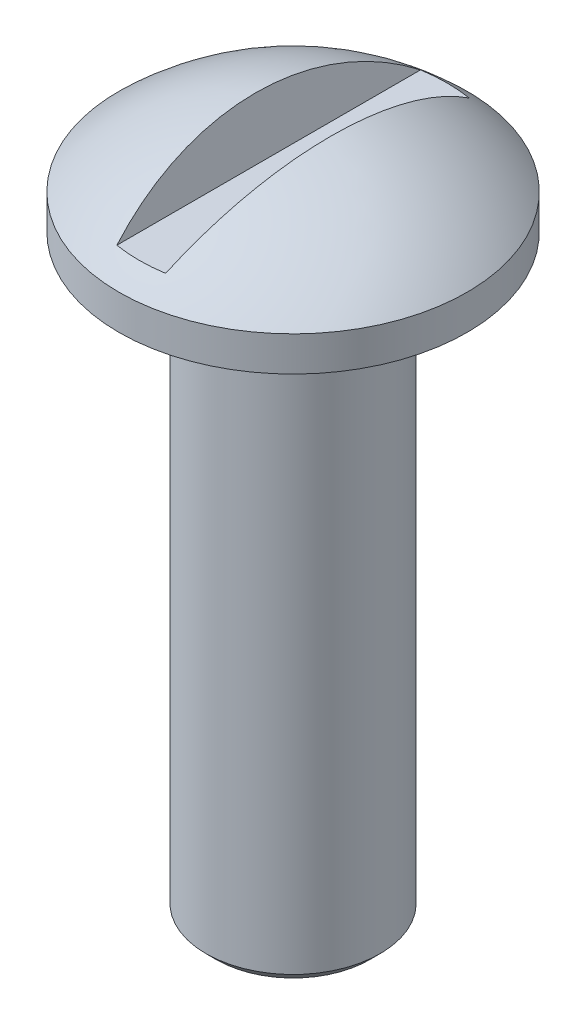
SolidWorks part; units mm, degrees
ref_plane "Front Plane" through (0, 0, 0) normal (0, 0, 1) x (1, 0, 0)
ref_plane "Top Plane" through (0, 0, 0) normal (0, 1, 0) x (1, 0, 0)
ref_plane "Right Plane" through (0, 0, 0) normal (1, 0, 0) x (0, 0, -1)
sketch "Sketch5" plane through (0, 0, 0) normal (0, 0, 1) x (1, 0, 0)
  line L0 (0, 0) -> (-6.35, 0)
  line L1 (-6.35, 0) -> (-6.35, 43.18)
  line L3 (0, 43.18) -> (0, 0)
  line L4 (0, 0) -> (0, -4.4813) construction
  line L5 (-6.35, 43.18) -> (-12.7, 43.18)
  line L6 (-12.7, 43.18) -> (-12.7, 45.72)
  line L7 (-12.7, 45.72) -> (0, 45.72)
  line L8 (0, 45.72) -> (0, 43.18)
  point P11 (-6.35, 0)
  point P12 (0, 0)
  dimension "D1" = 12.7
  dimension "D2" = 43.18
  dimension "D3" = 25.4
  dimension "D4" = 2.54
revolve "Revolve2" add sketch "Sketch5" angle 360 about L4
dome "Dome1" faces to dome 1 distance 5.08 reverse direction no elliptical dome no face at (0, 45.72, 12.7) parameters "D1"=5.08
sketch "Sketch7" plane through (0, 0, 0) normal (0, 0, 1) x (1, 0, 0)
  line L0 (0, 0) -> (0, 58.8957) construction
  line L1 (-6.35, 0) -> (6.35, 0) construction
  line L2 (-2.7425, 50.5946) -> (-1.7767, 46.99)
  line L3 (-1.7767, 46.99) -> (1.7767, 46.99)
  line L4 (-6.35, 43.18) -> (6.35, 43.18) construction
  line L5 (2.7425, 50.5946) -> (1.7767, 46.99)
  arc A0 (12.7, 45.72) -> (-12.7, 45.72) centre (0, 32.385) ccw construction
  point P13 (0, 46.99)
  dimension "D1" = 15
  dimension "D2" = 3.81
extrude "Cut-Extrude2" cut sketch "Sketch7" against normal through all both and the other way through all flip side to cut
chamfer "Chamfer1" distance 0.762 angle 45 1 edges at (0, 0, 6.35)
